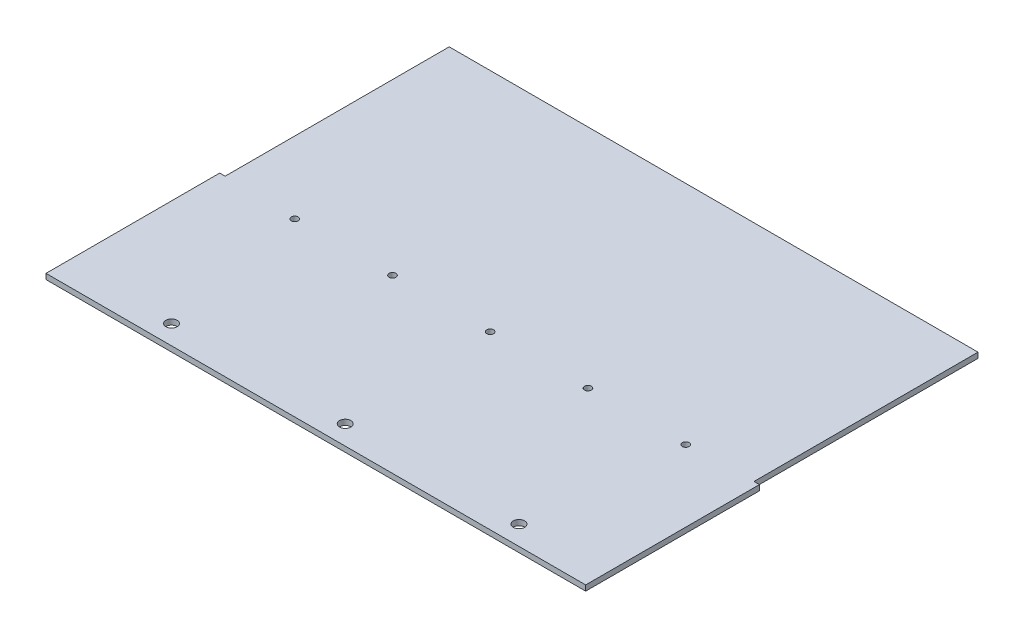
SolidWorks part; units mm, degrees
material "Custom Plastic"
ref_plane "X-Y Datum" through (0, 0, 0) normal (0, 0, 1) x (1, 0, 0)
ref_plane "X-Z Datum" through (0, 0, 0) normal (0, 1, 0) x (1, 0, 0)
ref_plane "Y-Z Datum" through (0, 0, 0) normal (1, 0, 0) x (0, 0, -1)
sketch "Sketch1" plane through (0, 0, 0) normal (0, 0, 1) x (1, 0, 0)
  line L1 (-157.79, -1.5875) -> (157.79, -1.5875)
  line L2 (-157.79, -1.5875) -> (-157.79, 1.5875)
  line L3 (-157.79, 1.5875) -> (157.79, 1.5875)
  line L4 (157.79, -1.5875) -> (157.79, 1.5875)
  line L5 (-157.79, -1.5875) -> (157.79, 1.5875) construction
  line L6 (-157.79, 1.5875) -> (157.79, -1.5875) construction
  point P0 (0, 0)
  dimension "D1" = 315.58
  dimension "D2" = 3.175
extrude "Boss-Extrude1" add sketch "Sketch1" along normal blind 232.6
sketch "Sketch5" plane through (0, 1.5875, 0) normal (0, 1, 0) x (1, 0, 0)
  line L15 (-157.79, 0) -> (-154.615, 0)
  line L16 (-157.79, 0) -> (-157.79, -131)
  line L17 (-157.79, -131) -> (-154.615, -131)
  line L18 (-154.615, 0) -> (-154.615, -131)
  dimension "D3" = 3.175
  dimension "D4" = 131
extrude "Cut-Extrude2" cut sketch "Sketch5" against normal through all and the other way through all
mirror "Mirror1" about plane through (0, 0, 0) normal (1, 0, 0) of "Cut-Extrude2"
sketch "Sketch7" plane through (0, -1.5875, 0) normal (0, -1, 0) x (1, 0, 0)
  line L0 (110.4954, 221.3083) -> (104.4954, 221.3083) construction
  circle A0 centre (107.4954, 221.3083) radius 3.302
  dimension "D1" = 6.604
extrude "Cut-Extrude3" cut sketch "Sketch7" against normal through all
pattern_linear "LPattern1" count 3 spacing 101.6 along (-1, 0, 0) of "Cut-Extrude3"
sketch "Sketch8" plane through (0, -1.5875, 0) normal (0, -1, 0) x (1, 0, 0)
  line L0 (-154.615, 131) -> (-154.615, 0) construction
  line L2 (-157.79, 232.6) -> (157.79, 232.6) construction
  circle A0 centre (-112.6329, 132.2875) radius 2
  point P2 (0, 0)
  dimension "D1" = 41.9821
  dimension "D3" = 4
  dimension "D2" = 100.3125
extrude "Cut-Extrude4" cut sketch "Sketch8" against normal through all
pattern_linear "LPattern2" count 5 spacing 57.15 along (1, 0, 0) of "Cut-Extrude4"
